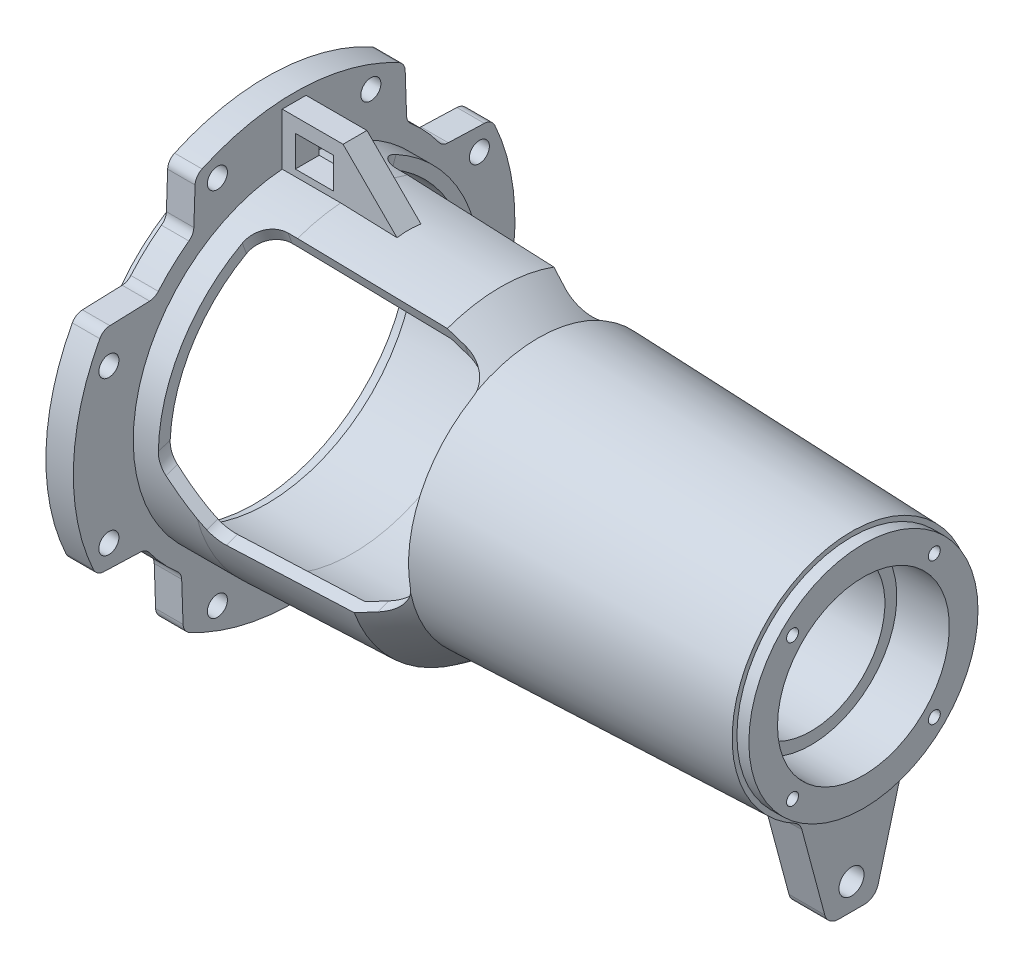
SolidWorks part; units mm, degrees
ref_plane "Front Plane" through (0, 0, 0) normal (0, 0, 1) x (1, 0, 0)
ref_plane "Top Plane" through (0, 0, 0) normal (0, 1, 0) x (1, 0, 0)
ref_plane "Right Plane" through (0, 0, 0) normal (1, 0, 0) x (0, 0, -1)
sketch "Sketch1" plane through (0, 0, 0) normal (0, 0, 1) x (1, 0, 0)
  line L0 (0, 0) -> (265, 0) construction
  line L1 (0, 70) -> (0, 65)
  line L2 (0, 65) -> (5, 65)
  line L3 (0, 70) -> (5, 70)
  line L4 (5, 65) -> (5, 62.5)
  line L5 (5, 62.5) -> (41, 62.5)
  line L6 (41, 62.5) -> (103, 60.3349)
  line L7 (103, 60.3349) -> (119, 49.5)
  line L8 (5, 70) -> (5, 92.5)
  line L9 (5, 92.5) -> (16.5, 92.5)
  line L10 (16.5, 92.5) -> (16.5, 67.4)
  line L11 (16.5, 67.4) -> (41, 67.4)
  line L12 (41, 67.4) -> (103, 65.2349)
  line L13 (103, 65.2349) -> (118.7281, 54.5841)
  line L14 (118.7281, 54.5841) -> (250, 50)
  line L15 (250, 50) -> (250, 48)
  line L16 (250, 48) -> (255, 48)
  line L17 (255, 48) -> (255, 36)
  line L18 (255, 36) -> (233, 36)
  line L19 (233, 36) -> (233, 31)
  line L20 (233, 31) -> (141, 31)
  line L21 (141, 31) -> (141, 36)
  line L22 (141, 36) -> (119, 36)
  line L23 (119, 36) -> (119, 49.5)
  point P5 (23, 62.5)
  point P28 (255, 42)
  dimension "D1" = 265
  dimension "D2" = 130
  dimension "D3" = 140
  dimension "D4" = 41
  dimension "D5" = 103
  dimension "D6" = 2
  dimension "D7" = 119
  dimension "D8" = 125
  dimension "D9" = 5
  dimension "D10" = 185
  dimension "D11" = 11.5
  dimension "D12" = 134.8
  dimension "D13" = 62
  dimension "D14" = 96
  dimension "D15" = 100
  dimension "D16" = 22
  dimension "D17" = 72
  dimension "D18" = 92
  dimension "D19" = 22
  dimension "D20" = 5
  dimension "D21" = 99
revolve "Revolve1" add sketch "Sketch1" angle 360 about L0
ref_plane "Plane1" through (27, 0, 0) normal (1, 0, 0) x (0, 0, -1)
sketch "Sketch2" plane through (27, 0, 0) normal (1, 0, 0) x (0, 0, -1)
  line L0 (0, 0) -> (-92.5, 0) construction
  line L1 (-16.417, 45.1052) -> (-23.9414, 65.7785)
  line L2 (-45.1052, -16.417) -> (-65.7785, -23.9414)
  line L3 (-16.417, 45.1052) -> (0, 0) construction
  line L4 (-45.1052, -16.417) -> (0, 0) construction
  circle A0 centre (0, 0) radius 92.5 construction
  arc A1 (-16.417, 45.1052) -> (-45.1052, -16.417) centre (0, 0) ccw
  arc A2 (-23.9414, 65.7785) -> (-65.7785, -23.9414) centre (0, 0) ccw
  dimension "D3" = 48
  dimension "D4" = 70
  dimension "D1" = 70
  dimension "D2" = 20
extrude "Cut-Extrude1" cut sketch "Sketch2" along normal blind 92
chamfer "Chamfer1" distance 20 angle 45 1 edges at (27, -22.2142, 61.033)
fillet "Fillet1" radius 10 5 edges at (119, -17.7978, 48.8991) (119, 48.8991, 17.7978) (47, -22.1425, 60.8361) (27, 61.033, 22.2142) (27, -2.3392, 64.903)
mirror "Mirror1" about plane through (0, 0, 0) normal (0, 0, 1) of "Cut-Extrude1", "Chamfer1", "Fillet1"
sketch "Sketch3" plane through (5, 0, 0) normal (-1, 0, 0) x (0, 0, 1)
  line L0 (0, 0) -> (0, 92.5) construction
  line L1 (0, 0) -> (65.4074, 65.4074) construction
  line L2 (41.3841, 82.7261) -> (42.1056, 62.0655)
  line L3 (58.2959, 47.1867) -> (80.0039, 46.4286)
  circle A0 centre (0, 0) radius 92.5 construction
  arc A1 (58.2959, 47.1867) -> (42.1056, 62.0655) centre (0, 0) ccw
  circle A2 centre (0, 0) radius 92.5
  circle M6 centre (0, 0) radius 92.5
  dimension "D4" = 75
  dimension "D1" = 45
  dimension "D2" = 53
  dimension "D3" = 94
  dimension "D5" = 47
extrude "Cut-Extrude2" cut sketch "Sketch3" against normal up to next contours A1 L3 L2 M6 region at (5, 61.5449, 57.3815)
fillet "Fillet2" radius 5 4 edges at (10.75, 46.4286, 80.0039) (10.75, 47.1867, 58.2959) (10.75, 62.0655, 42.1056) (10.75, 82.7261, 41.3841)
pattern_circular "CirPattern1" count 4 over 360 about axis through (0, 0, 0) along (-1, 0, 0) of "Cut-Extrude2", "Fillet2"
hole_wizard "Ø8.4 (8.4) Diameter Hole1" positions "Sketch4" profile "Sketch6" hole size "Ø8.4" standard "ANSI Metric" end condition through all
sketch "Sketch4" plane through (5, 0, 0) normal (-1, 0, 0) x (0, 0, 1)
  line L0 (0, 0) -> (0, 92.5) construction
  line L1 (-32.1454, 77.6059) -> (0, 0) construction
  arc A0 (38.578, 84.0713) -> (-43.9031, 81.4173) centre (0, 0) ccw construction
  point P0 (-32.1454, 77.6059)
  dimension "D1" = 22.5
  dimension "D2" = 84
sketch "Sketch6" plane through (5, 77.6059, -32.1454) normal (0, 1, 0) x (0, 0, 1)
  line L0 (0, 0) -> (0, 250)
  line L1 (0, 250) -> (4.2, 250)
  line L2 (4.2, 250) -> (4.2, 0)
  line L5 (4.2, 0) -> (0, 0)
  line L11 (0, -6.35) -> (0, 107.95) construction
  dimension "Thru Hole Dia." = 8.4
  dimension "Thru Hole Depth" = 250
pattern_circular "CirPattern2" count 8 over 360 about axis through (0, 0, 0) along (-1, 0, 0) of "Ø8.4 (8.4) Diameter Hole1"
sketch "Sketch7" plane through (250, 0, 0) normal (1, 0, 0) x (0, 0, -1)
  line L0 (-21.4816, -45.1502) -> (-10, -88)
  line L1 (-10, -88) -> (10, -88)
  line L2 (10, -88) -> (21.4816, -45.1502)
  line L3 (0, 0) -> (0, -88) construction
  circle A0 centre (0, 0) radius 50 construction
  circle A1 centre (0, 0) radius 50
  circle M4 centre (0, 0) radius 50
  dimension "D1" = 20
  dimension "D2" = 30
  dimension "D3" = 88
extrude "Boss-Extrude1" add sketch "Sketch7" against normal blind 15 contours L3 L0 L1 M4 | A1 L3 L1 L2 region at (250, -65.9292, 8.232) region at (250, -65.9292, -8.232)
fillet "Fillet3" radius 6 4 edges at (242.5, -88, -10) (242.5, -88, 10)
hole_wizard "Ø10.5 (10.5) Diameter Hole1" positions "Sketch8" profile "Sketch9" hole size "Ø10.5" standard "ANSI Metric" end condition up to next
sketch "Sketch8" plane through (250, 0, 0) normal (1, 0, 0) x (0, 0, -1)
  point P0 (0, -77)
  dimension "D1" = 77
sketch "Sketch9" plane through (250, -77, 0) normal (0, 1, 0) x (0, 0, -1)
  line L0 (0, 0) -> (0, 15)
  line L1 (0, 15) -> (5.25, 15)
  line L2 (5.25, 15) -> (5.25, 0)
  line L5 (5.25, 0) -> (0, 0)
  line L11 (0, -6.35) -> (0, 107.95) construction
  dimension "Thru Hole Dia." = 10.5
  dimension "Thru Hole Depth" = 15
hole_wizard "M6x1.0 Tapped Hole1" positions "Sketch10" profile "Sketch12" tap size "M6x1.0" standard "ANSI Metric"
sketch "Sketch10" plane through (255, 0, 0) normal (1, 0, 0) x (0, 0, -1)
  line L0 (-29.6985, 29.6985) -> (0, 0) construction
  line L1 (0, 0) -> (0, 48) construction
  circle A0 centre (0, 0) radius 48 construction
  point P0 (-29.6985, 29.6985)
  dimension "D1" = 45
  dimension "D2" = 42
sketch "Sketch12" plane through (255, 29.6985, 29.6985) normal (0, 1, 0) x (0, 0, -1)
  line L0 (0, 0) -> (0, 25.5022)
  line L1 (0, 25.5022) -> (2.5, 24)
  line L2 (2.5, 24) -> (2.5, 0)
  line L5 (2.5, 0) -> (0, 0)
  line L10 (0, 25.5022) -> (-2.5, 24) construction
  line L11 (0, -6.35) -> (0, 107.95) construction
  dimension "Tap Drill Dia." = 5
  dimension "Tap Drill Depth" = 24
  dimension "Drill Angle" = 118
cosmetic thread "Hole Thread1" parameters "D1"=20, "D2"=6
hole_wizard "M6x1.0 Tapped Hole2" positions "Sketch13" profile "Sketch14" tap size "M6x1.0" standard "ANSI Metric"
sketch "Sketch13" plane through (119, 0, 0) normal (-1, 0, 0) x (0, 0, 1)
  line L0 (0, 0) -> (0, 49.5) construction
  line L1 (0, 0) -> (29.6985, 29.6985) construction
  arc A0 (25.9778, 42.1355) -> (-25.9778, 42.1355) centre (0, 0) ccw construction
  point P0 (29.6985, 29.6985)
  dimension "D1" = 45
  dimension "D2" = 42
sketch "Sketch14" plane through (119, 29.6985, 29.6985) normal (0, 1, 0) x (0, 0, 1)
  line L0 (0, 0) -> (0, 26.5022)
  line L1 (0, 26.5022) -> (2.5, 25)
  line L2 (2.5, 25) -> (2.5, 0)
  line L5 (2.5, 0) -> (0, 0)
  line L10 (0, 26.5022) -> (-2.5, 25) construction
  line L11 (0, -6.35) -> (0, 107.95) construction
  dimension "Tap Drill Dia." = 5
  dimension "Tap Drill Depth" = 25
  dimension "Drill Angle" = 118
cosmetic thread "Hole Thread2" parameters "D1"=20, "D2"=6
pattern_circular "CirPattern3" count 4 over 360 about axis through (255, 0, 0) along (-1, 0, 0) of "M6x1.0 Tapped Hole1", "M6x1.0 Tapped Hole2"
cosmetic thread "Hole Thread3" parameters "D1"=20, "D2"=6
cosmetic thread "Hole Thread4" parameters "D1"=20, "D2"=6
cosmetic thread "Hole Thread5" parameters "D1"=20, "D2"=6
cosmetic thread "Hole Thread6" parameters "D1"=20, "D2"=6
cosmetic thread "Hole Thread7" parameters "D1"=20, "D2"=6
cosmetic thread "Hole Thread8" parameters "D1"=20, "D2"=6
sketch "Sketch15" plane through (0, 0, 0) normal (0, 0, 1) x (1, 0, 0)
  line L0 (16.5, 89) -> (42, 89)
  line L1 (16.5, 81.4173) -> (16.5, 92.5) construction
  line L2 (42, 89) -> (67, 64)
  line L3 (67, 64) -> (16.5, 64)
  line L4 (16.5, 77.1908) -> (16.5, 60.5297) construction
  line L5 (16.5, 64) -> (16.5, 89)
  line L7 (22, 83) -> (38, 83)
  line L8 (22, 83) -> (22, 70)
  line L9 (22, 70) -> (38, 70)
  line L10 (38, 83) -> (38, 70)
  dimension "D1" = 89
  dimension "D2" = 25.5
  dimension "D3" = 45
  dimension "D4" = 25
  dimension "D5" = 5.5
  dimension "D6" = 6
  dimension "D7" = 13
  dimension "D8" = 16
extrude "Boss-Extrude2" add sketch "Sketch15" along normal mid plane 10
